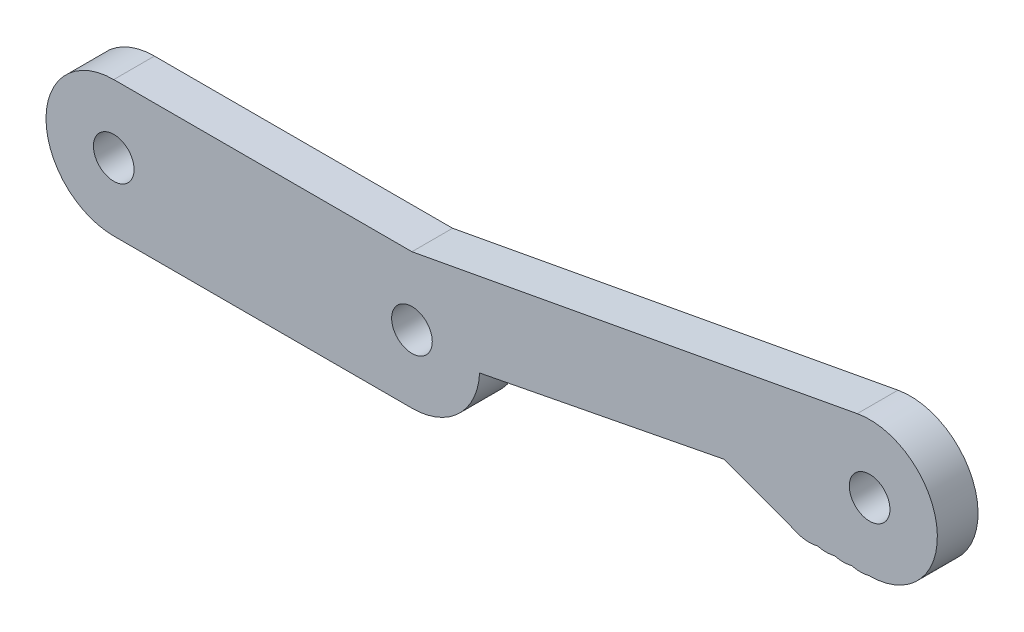
SolidWorks part; units mm, degrees
ref_plane "Piano frontale" through (0, 0, 0) normal (0, 0, 1) x (1, 0, 0)
ref_plane "Piano superiore" through (0, 0, 0) normal (0, 1, 0) x (1, 0, 0)
ref_plane "Piano destro" through (0, 0, 0) normal (1, 0, 0) x (0, 0, -1)
sketch "Schizzo1" plane through (0, 0, 0) normal (0, 0, 1) x (1, 0, 0)
  line L0 (0, 0) -> (22, 0) construction
  line L1 (0, 5) -> (22, 5)
  line L2 (0, -5) -> (22, -5)
  line L3 (22, 0) -> (55.7665, 6.1658) construction
  line L4 (22, 5) -> (54.8564, 11.0823)
  line L5 (22, 0) -> (22, -5) construction
  line L6 (22, -1.5) -> (22, -5) construction
  line L7 (22, -5) -> (22, -1.5) construction
  line L8 (22, -1.5) -> (22, -3.25) construction
  line L9 (22, 0) -> (22, -1.5) construction
  line L10 (22, 0) -> (22, -1.0038) construction
  line L11 (22, -1.0038) -> (23.1147, -1.0038) construction
  line L12 (60.7665, 6.1658) -> (60.7665, 1.1658)
  line L13 (50.6665, 1.1658) -> (60.7665, 1.1658) construction
  line L14 (55.7665, 6.1658) -> (55.7665, 4.6658) construction
  line L15 (55.7665, 6.1658) -> (55.7665, 5.1273) construction
  line L16 (55.7665, 5.1273) -> (54.6841, 5.1273) construction
  line L17 (23.1147, -1.0038) -> (54.6841, 5.1273) construction
  line L18 (50.6665, 1.1658) -> (45.0418, 3.2547)
  line L19 (45.0418, 3.2547) -> (26.9937, -0.2504)
  line L20 (55.7665, 1.1658) -> (55.7015, 1.1658)
  line L21 (53.8115, 1.1658) -> (53.8115, 1.0811) construction
  circle A0 centre (0, 0) radius 1.5
  circle A1 centre (22, 0) radius 1.5
  circle A2 centre (0, 0) radius 5
  circle A3 centre (22, 0) radius 5
  circle A4 centre (55.7665, 6.1658) radius 1.5
  circle A5 centre (55.7665, 6.1658) radius 5
  arc A6 (50.6665, 1.1658) -> (51.9215, 1.1658) centre (51.294, 3.4658) ccw
  arc A7 (51.9215, 1.1658) -> (53.1815, 1.1658) centre (52.5515, 3.4642) ccw
  arc A8 (54.4415, 1.1658) -> (53.1815, 1.1658) centre (53.8115, 3.4658) cw
  arc A9 (54.4415, 1.1658) -> (55.7015, 1.1658) centre (55.0715, 3.4658) ccw
  arc A10 (55.7015, 1.1658) -> (56.9615, 1.1658) centre (56.3315, 3.4658) ccw
  arc A11 (58.2215, 1.1658) -> (56.9615, 1.1658) centre (57.5915, 3.4658) cw
  arc A12 (58.2215, 1.1658) -> (59.4815, 1.1658) centre (58.8515, 3.4658) ccw
  arc A13 (59.4815, 1.1658) -> (60.7665, 1.1658) centre (60.124, 3.5166) ccw
  point P11 (0.0548, -1.499)
  point P12 (21.993, -1.5)
  point P13 (-0.0196, 1.4999)
  point P15 (21.993, -1.5)
  point P19 (54.8564, 11.0823)
  point P21 (51.2915, 1.1658)
  point P32 (50.6665, 1.1658)
  point P33 (52.5515, 1.1658)
  point P34 (53.1815, 1.1658)
  point P35 (53.8115, 1.1658)
  point P36 (54.4415, 1.1658)
  point P37 (55.0715, 1.1658)
  point P38 (51.9215, 1.1658)
  point P39 (55.7015, 1.1658)
  point P40 (56.3315, 1.1658)
  point P41 (56.9615, 1.1658)
  point P42 (57.5915, 1.1658)
  point P43 (58.2215, 1.1658)
  point P44 (58.8515, 1.1658)
  point P45 (59.4815, 1.1658)
  point P46 (60.1115, 1.1676)
  point P64 (51.294, 1.0817)
  point P65 (52.5515, 1.081)
  point P66 (55.0715, 1.0811)
  point P67 (53.8115, 1.0811)
  point P68 (51.2915, 1.1658)
  point P69 (56.3315, 1.0811)
  point P70 (57.5915, 1.0811)
  point P71 (58.8515, 1.0811)
  point P72 (60.124, 1.0796)
  dimension "D1" = 3
  dimension "D2" = 3
  dimension "D4" = 10
  dimension "D5" = 3.5
  dimension "D8" = 3.5002
  dimension "D9" = 3
  dimension "D10" = 10
  dimension "D42" = 32.8564
  dimension "D35" = 0.0841
  dimension "D3" = 22
  dimension "D6" = 10
  dimension "D7" = 3.5014
  dimension "D11" = 5
  dimension "D12" = 6.0038
  dimension "D13" = 10.1
  dimension "D14" = 6
  dimension "D15" = 18.0481
  dimension "D16" = 2.0889
  dimension "D17" = 4.9937
  dimension "D18" = 0.625
  dimension "D19" = 0.63
  dimension "D20" = 0.63
  dimension "D21" = 0.63
  dimension "D22" = 0.63
  dimension "D23" = 0.63
  dimension "D24" = 0.63
  dimension "D25" = 0.63
  dimension "D26" = 0.63
  dimension "D27" = 0.63
  dimension "D28" = 0.63
  dimension "D29" = 0.63
  dimension "D30" = 0.63
  dimension "D31" = 0.63
  dimension "D32" = 0.63
  dimension "D33" = 0.655
  dimension "D34" = 1.255
  dimension "D36" = 1.26
  dimension "D37" = 0.0848
  dimension "D38" = 1.26
  dimension "D39" = 0.0847
  dimension "D40" = 1.26
  dimension "D41" = 0.63
  dimension "D43" = 5
  dimension "D44" = 0.0847
  dimension "D45" = 0.63
  dimension "D46" = 1.26
  dimension "D47" = 0.0847
  dimension "D48" = 0.63
  dimension "D49" = 0.0847
  dimension "D50" = 1.26
  dimension "D51" = 0.63
  dimension "D52" = 1.26
  dimension "D53" = 0.0847
  dimension "D54" = 0.63
  dimension "D55" = 1.285
  dimension "D56" = 0.0889
  dimension "D57" = 0.6425
extrude "Estrusione-Estrusione1" add sketch "Schizzo1" along normal blind 3 contours A2 A0 | A3 L1 A2 L2 | A3 A1 | A8 A9 L20 A5 L4 A3 L19 L18 A6 A7 | A5 A4 region at (11, 0, 0) region at (3.4355, 3.4355, 0) region at (39.465, 4.923, 0) region at (25.4355, 3.4355, 0) region at (58.8736, 9.9009, 0)
